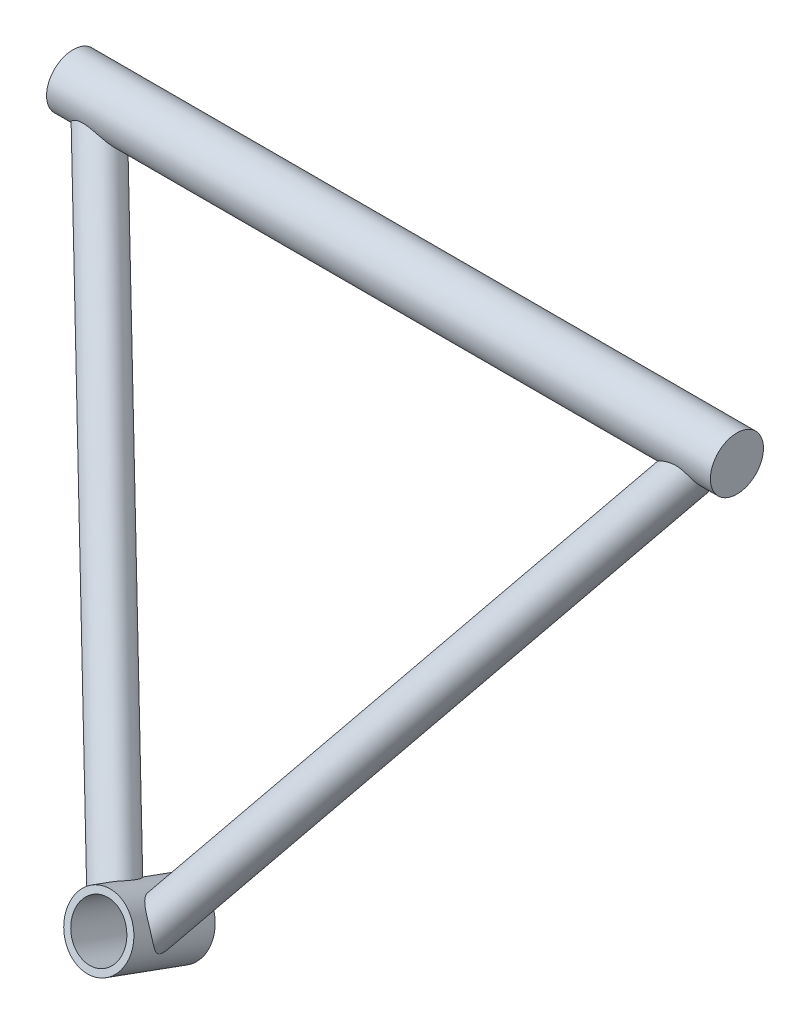
SolidWorks part; units mm, degrees
material "AISI 4130 Steel, normalized at 870C"
ref_plane "Front Plane" through (0, 0, 0) normal (0, 0, 1) x (1, 0, 0)
ref_plane "Top Plane" through (0, 0, 0) normal (0, 1, 0) x (1, 0, 0)
ref_plane "Right Plane" through (0, 0, 0) normal (1, 0, 0) x (0, 0, -1)
sketch "Sketch3" plane through (0, 0, 0) normal (0, 1, 0) x (1, 0, 0)
  line L0 (-5.08, -6.35) -> (5.08, -6.35) construction
  line L2 (0, -88.2205) -> (0, 88.2205) construction
  line L3 (5.08, 0) -> (-5.08, 0) construction
  dimension "D1" = 5.08
  dimension "D2" = 10.16
  dimension "D3" = 6.35
  dimension "D4" = 10.16
  dimension "D5" = 5.08
ref_plane "Plane1" through (0, 2.9005, 4.4664) normal (0, 0.5446, 0.8387) x (1, 0, 0)
ref_plane "Plane3" through (0, 0, 0) normal (0, 0.342, 0.9397) x (-1, 0, 0)
sketch "Sketch1" plane through (0, 0, 0) normal (0, 0.342, 0.9397) x (1, 0, 0)
  circle A0 centre (0, 0) radius 15.875
  dimension "D1" = 31.75
extrude "Boss-Extrude1" add sketch "Sketch1" along normal mid plane 41.402 contours A0
sketch "Sketch4" plane through (0, 2.9005, 4.4664) normal (0, 0.5446, 0.8387) x (1, 0, 0)
  line L0 (-5.08, -3.4585) -> (-144.78, 238.509)
  line L2 (0, -90.5202) -> (0, 90.5202) construction
  dimension "D2" = 30
  dimension "D3" = 279.4
sweep "Sweep1" add path "Sketch4" circular profile diameter 19.05 parameters "D3"=19.05
sketch "Sketch15" plane through (0, 2.9005, 4.4664) normal (0, 0.5446, 0.8387) x (1, 0, 0)
  line L0 (5.08, -3.4585) -> (144.78, 238.509)
  line L1 (0, -90.5202) -> (0, 90.5202) construction
  dimension "D1" = 279.4
  dimension "D2" = 30
sweep "Sweep2" add path "Sketch15" circular profile diameter 19.05 parameters "D3"=19.05
sketch "Sketch36" plane through (-139.4724, 202.6005, -131.5703) normal (-0.5, 0.7263, -0.4717) x (0.8645, 0.3864, -0.3214)
  circle A0 centre (-6.4328, -4.9539) radius 7.9375
  dimension "D1" = 15.875
extrude "Cut-Extrude2" cut sketch "Sketch36" against normal up to surface (288.7252 mm away) up to face at (15.5539, -1.3152, 5.6742)
sketch "Sketch37" plane through (139.4724, 202.6005, -131.5703) normal (0.5, 0.7263, -0.4717) x (0.8645, -0.3864, 0.3214)
  circle A0 centre (6.4328, -4.9539) radius 7.9375
  dimension "D1" = 15.875
extrude "Cut-Extrude3" cut sketch "Sketch37" against normal up to surface (264.4331 mm away) up to face at (9.5838, -7.621, 16.0643)
sketch "Sketch77" plane through (0, 7.0802, 19.4526) normal (0, 0.342, 0.9397) x (1, 0, 0)
  circle A1 centre (0, 0) radius 15.875
extrude "Boss-Extrude2" add sketch "Sketch77" against normal up to surface (41.402 mm away) up to face at (0, -21.9978, -14.023)
sketch "Sketch2" plane through (0, -7.0802, -19.4526) normal (0, -0.342, -0.9397) x (-1, 0, 0)
  circle A0 centre (0, 0) radius 12.7
  dimension "D1" = 25.4
extrude "Cut-Extrude1" cut sketch "Sketch2" against normal up to next
ref_plane "Plane2" through (0, 0, -127) normal (0, 0, 1) x (1, 0, 0)
ref_plane "Plane4" through (0, 177.8, 0) normal (0, 1, 0) x (1, 0, 0)
sketch "Sketch40" plane through (-106.934, 0, -127) normal (0, 0, 1) x (1, 0, 0)
  line L0 (108.4431, 207.01) -> (50108.4431, 207.01) construction
  line L1 (-51.816, 207.01) -> (265.684, 207.01)
  point P0 (106.934, 207.01)
  point P1 (106.934, 207.01)
  dimension "D1" = 317.5
  dimension "D5" = 207.01
sweep "Sweep5" add path "Sketch40" circular profile diameter 25.4 parameters "D3"=25.4
sketch "Sketch118" plane through (0, 177.8, 0) normal (0, 1, 0) x (1, 0, 0)
  line L0 (0, 148.2378) -> (-165.1, 148.2378)
  line L1 (0, 148.2378) -> (165.1, 148.2378)
  dimension "D1" = 165.1
  dimension "D2" = 165.1
sweep "Sweep4" [suppressed] add path "Sketch118" circular profile diameter 25.4 parameters "D3"=25.4
